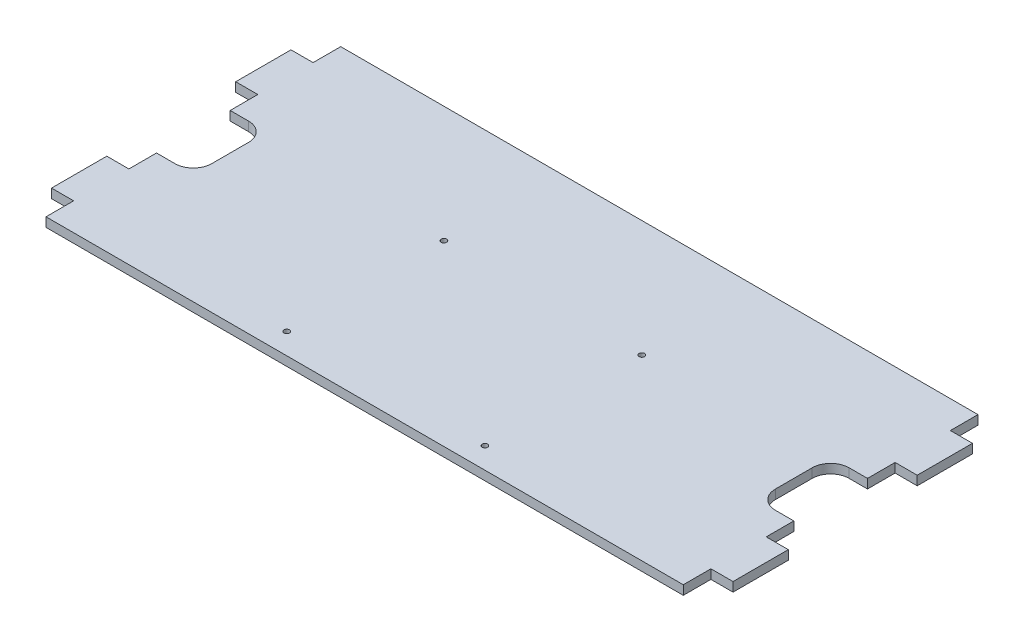
SolidWorks part; units mm, degrees
ref_plane "前基準面" through (0, 0, 0) normal (0, 0, 1) x (1, 0, 0)
ref_plane "上基準面" through (0, 0, 0) normal (0, 1, 0) x (1, 0, 0)
ref_plane "右基準面" through (0, 0, 0) normal (1, 0, 0) x (0, 0, -1)
sketch "草圖1" plane through (0, 0, 0) normal (0, 1, 0) x (1, 0, 0)
  line L0 (173, -65) -> (185, -65)
  line L1 (173, 80) -> (-173, 80)
  line L2 (173, 80) -> (173, 65)
  line L3 (173, -80) -> (-173, -80)
  line L4 (-173, 80) -> (-173, 65)
  line L5 (0, -80) -> (0, 80) construction
  line L6 (173, 0) -> (-173, 0) construction
  line L7 (-173, 65) -> (-185, 65)
  line L9 (-173, 35) -> (-185, 35)
  line L10 (-185, 65) -> (-185, 35)
  line L11 (-173, -35) -> (-185, -35)
  line L13 (-173, -65) -> (-185, -65)
  line L14 (-185, -35) -> (-185, -65)
  line L15 (185, -35) -> (185, -65)
  line L16 (173, -35) -> (185, -35)
  line L18 (173, 35) -> (185, 35)
  line L19 (185, 65) -> (185, 35)
  line L20 (173, 65) -> (185, 65)
  line L22 (-173, 35) -> (-173, -35)
  line L23 (-173, -65) -> (-173, -80)
  line L24 (173, 35) -> (173, -35)
  line L25 (173, -65) -> (173, -80)
  point P0 (0, 0)
  point P23 (0, 0)
  dimension "D1" = 346
  dimension "D2" = 160
  dimension "D3" = 30
  dimension "D4" = 12
  dimension "D5" = 70
extrude "填料-伸長1" add sketch "草圖1" along normal blind 5
sketch "草圖2" plane through (0, 5, 0) normal (0, 1, 0) x (1, 0, 0)
  line L0 (-198.9814, -25.875) -> (243.2492, -25.875) construction
  line L1 (-173, 35) -> (-173, -35) construction
  line L2 (-173, -20) -> (-163, -20)
  line L3 (-173, -20) -> (-173, 20)
  line L4 (-173, 20) -> (-163, 20)
  line L5 (-153, -10) -> (-153, 10)
  line L6 (0, 100.6086) -> (0, -91.6656) construction
  line L7 (173, 20) -> (163, 20)
  line L8 (46.9507, -106.8687) -> (50.0807, -109.5516) construction
  line L9 (153, -10) -> (153, 10)
  line L10 (173, -20) -> (163, -20)
  line L11 (173, -20) -> (173, 20)
  line L12 (-173, -80) -> (173, -80) construction
  line L13 (55, 18) -> (-55, 18) construction
  line L14 (55, 18) -> (55, -70) construction
  line L15 (55, -70) -> (-55, -70) construction
  line L16 (-55, 18) -> (-55, -70) construction
  line L17 (0, -70) -> (0, 18) construction
  arc A0 (-163, -20) -> (-153, -10) centre (-163, -10) ccw
  arc A1 (-163, 20) -> (-153, 10) centre (-163, 10) cw
  arc A2 (163, 20) -> (153, 10) centre (163, 10) ccw
  arc A3 (153, -10) -> (163, -20) centre (163, -10) ccw
  circle A4 centre (-53.75, 16.75) radius 1.25 construction
  circle A8 centre (-53.75, 16.75) radius 1.5
  circle A9 centre (53.75, 16.75) radius 1.5
  circle A10 centre (53.75, -68.5) radius 1.5
  circle A11 centre (-53.75, -68.5) radius 1.5
  point P20 (-153, -20)
  point P23 (-153, 20)
  point P26 (153, 20)
  point P29 (153, -20)
  point P31 (0, 0)
  point P36 (0, 0)
  point P47 (0, 0)
  point P48 (0, 0)
  point P49 (0, 0)
  point P50 (0, 0)
  point P51 (0, -48.2031)
  point P52 (0, 0)
  point P53 (0, 0)
  dimension "D3" = 10
  dimension "D4" = 10
  dimension "D7" = 2.5
  dimension "D8" = 3
  dimension "D1" = 40
  dimension "D2" = 20
  dimension "D5" = 110
  dimension "D6" = 88
  dimension "D9" = 10
extrude "除料-伸長1" cut sketch "草圖2" against normal through all
